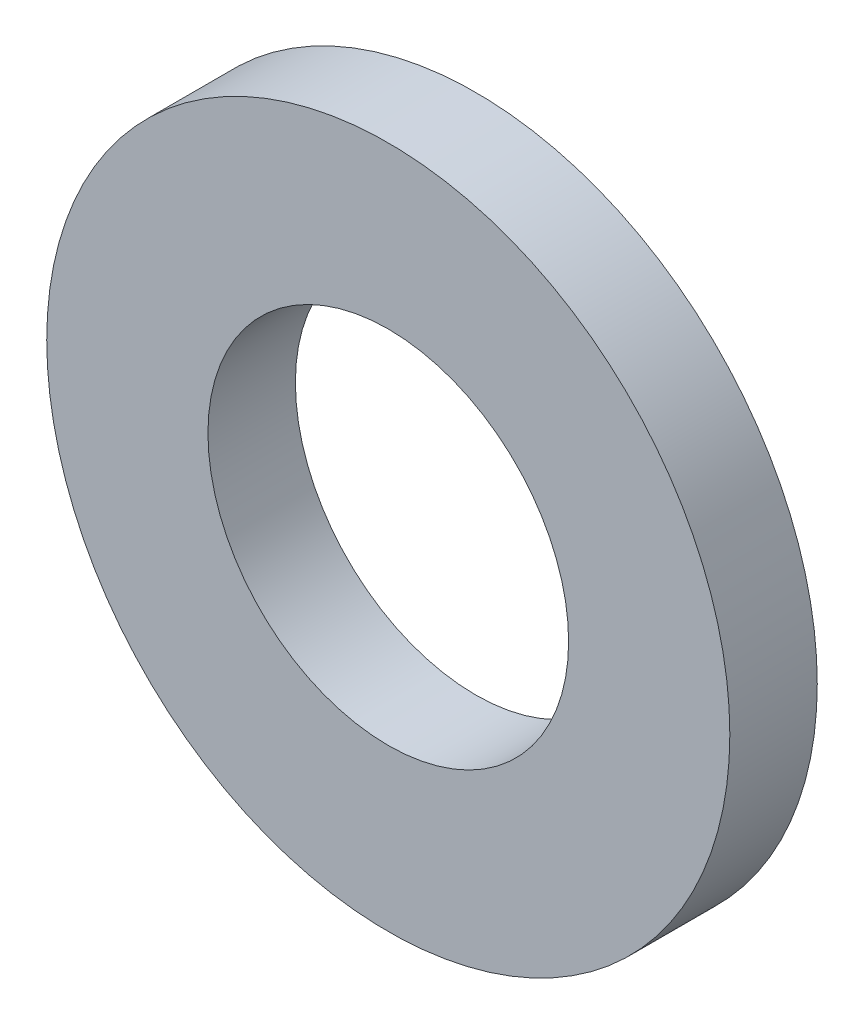
SolidWorks part; units mm, degrees
ref_plane "Front Plane" through (0, 0, 0) normal (0, 0, 1) x (1, 0, 0)
ref_plane "Top Plane" through (0, 0, 0) normal (0, 1, 0) x (1, 0, 0)
ref_plane "Right Plane" through (0, 0, 0) normal (1, 0, 0) x (0, 0, -1)
sketch "BodySke" plane through (0, 0, 0) normal (0, 1, 0) x (1, 0, 0)
  line L0 (0, 0) -> (0, 7.8986) construction
  line L2 (3.3, 1.6) -> (6.25, 1.6)
  line L3 (3.3, 1.6) -> (3.3, 0)
  line L4 (3.3, 0) -> (6.25, 0)
  line L5 (6.25, 1.6) -> (6.25, 0)
  dimension "Inner_dia" = 6.6
  dimension "Outer_dia" = 12.5
  dimension "Thickness" = 1.6
revolve "BaseBody" add sketch "BodySke" angle 360 about L0
